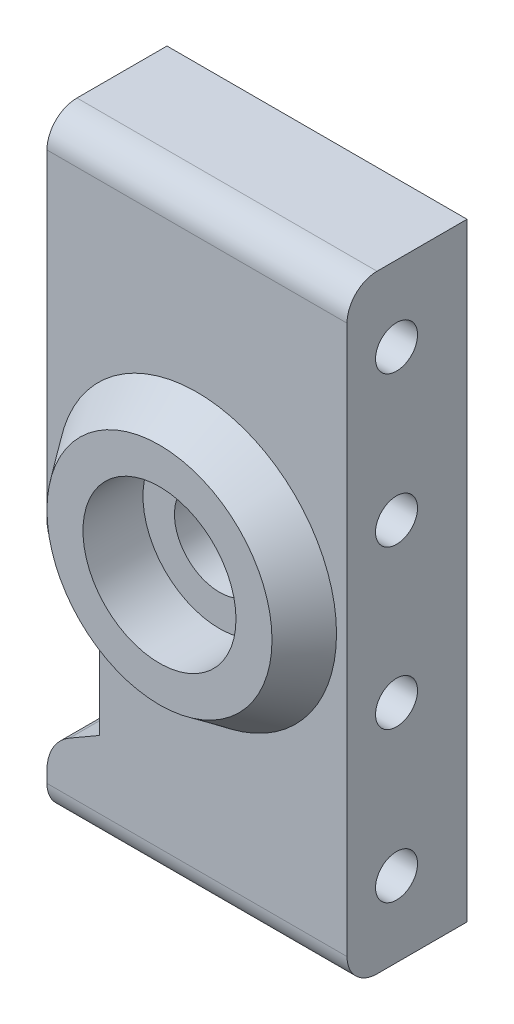
SolidWorks part; units mm, degrees
material "PLA_Holder_Ruleman"
ref_plane "Front Plane" through (0, 0, 0) normal (0, 0, 1) x (1, 0, 0)
ref_plane "Top Plane" through (0, 0, 0) normal (0, 1, 0) x (1, 0, 0)
ref_plane "Right Plane" through (0, 0, 0) normal (1, 0, 0) x (0, 0, -1)
sketch "Sketch1" plane through (0, 0, 0) normal (0, 0, 1) x (1, 0, 0)
  line L0 (-10, 20.2804) -> (-10, -20.2804)
  line L1 (-10, -20.2804) -> (10, -20.2804)
  line L2 (10, -20.2804) -> (10, 20.2804)
  line L3 (10, 20.2804) -> (-10, 20.2804)
  line L4 (-10, 20.2804) -> (10, -20.2804) construction
  line L11 (-10, -20.2804) -> (10, 20.2804) construction
  point P9 (0, 0)
  dimension "D1" = 20
  dimension "D2" = 40.5608
extrude "Boss-Extrude1" add sketch "Sketch1" against normal blind 8
sketch "Sketch6" plane through (10, 0, 0) normal (1, 0, 0) x (0, 0, -1)
  line L0 (0, -20.2804) -> (0, 20.2804) construction
  line L1 (3.3, -5.2652) -> (3.3, -15.2652) construction
  line L2 (3.3, 4.95) -> (3.3, 15.6283) construction
  line L3 (0, 0) -> (8, 0) construction
  line L4 (8, -20.2804) -> (8, 20.2804) construction
  line L5 (23.2424, -10.2652) -> (-16.6424, -10.2652) construction
  line L6 (8, -20.2804) -> (0, -20.2804) construction
  line L7 (23.2424, -0.25) -> (-16.6424, -0.25) construction
  circle A0 centre (3.3, -15.2652) radius 1.4
  circle A1 centre (3.3, -5.2652) radius 1.4
  circle A2 centre (3.3, 15.2652) radius 1.4
  circle A3 centre (3.3, 5.2652) radius 1.4
  point P15 (3.3, -10.2652)
  dimension "D1" = 2.8
  dimension "D2" = 4.7
  dimension "D3" = 10.0152
  dimension "D4" = 10
  dimension "D5" = 10.0152
extrude "Cut-Extrude1" cut sketch "Sketch6" against normal blind 10
sketch "Sketch8" plane through (0, 0, 0) normal (0, 0, 1) x (1, 0, 0)
  line L0 (-10, 20.2804) -> (10, -20.2804) construction
  circle A0 centre (0, 0) radius 7.5
  dimension "D1" = 15
extrude "Boss-Extrude2" add sketch "Sketch8" along normal blind 2.5
sketch "Sketch9" plane through (0, 0, 2.5) normal (0, 0, 1) x (1, 0, 0)
  circle A0 centre (0, 0) radius 5.1
  dimension "D1" = 10.2
extrude "Cut-Extrude3" cut sketch "Sketch9" against normal blind 4
sketch "Sketch10" plane through (0, 0, -1.5) normal (0, 0, 1) x (1, 0, 0)
  circle A0 centre (0, 0) radius 3
  dimension "D1" = 6
extrude "Cut-Extrude4" cut sketch "Sketch10" against normal up to surface (6.5 mm away) up to face at (0, 0, -8)
fillet "Fillet1" radius 2 2 edges at (0, -20.2804, 0) (0, 20.2804, 0) tangent propagation no
chamfer "Chamfer1" distance 1.8 distance2 2.5 1 edges at (7.5, 0, 0) first distance on face at (7.5, 0, 0)
sketch "Sketch11" plane through (-10, 0, 0) normal (-1, 0, 0) x (0, 0, 1)
  line L0 (-8, -10.2652) -> (0, -10.2652) construction
  line L1 (-8, 20.2804) -> (-8, -20.2804) construction
  line L2 (0, 18.2804) -> (0, -18.2804) construction
  line L3 (-8, -20.2804) -> (-2, -20.2804) construction
  line L4 (-8, -13.7652) -> (0, -13.7652)
  line L5 (-8, -6.7652) -> (0, -6.7652)
  line L6 (0, -6.7652) -> (0, -13.7652)
  line L7 (-8, -13.7652) -> (-8, -6.7652)
  dimension "D1" = 10.0152
  dimension "D2" = 3.5
  dimension "D3" = 3.5
extrude "Cut-Extrude5" cut sketch "Sketch11" against normal blind 3.5
chamfer "Chamfer2" distance 3.5 angle 30 2 edges at (-10, -13.7652, -4) (-10, -6.7652, -4) first distance on face at (-8.25, -13.7652, -4) first distance on face at (-8.25, -6.7652, -4)
fillet "Fillet2" radius 3 2 edges at (-10, -15.7859, -4) (-10, -4.7444, -4)
